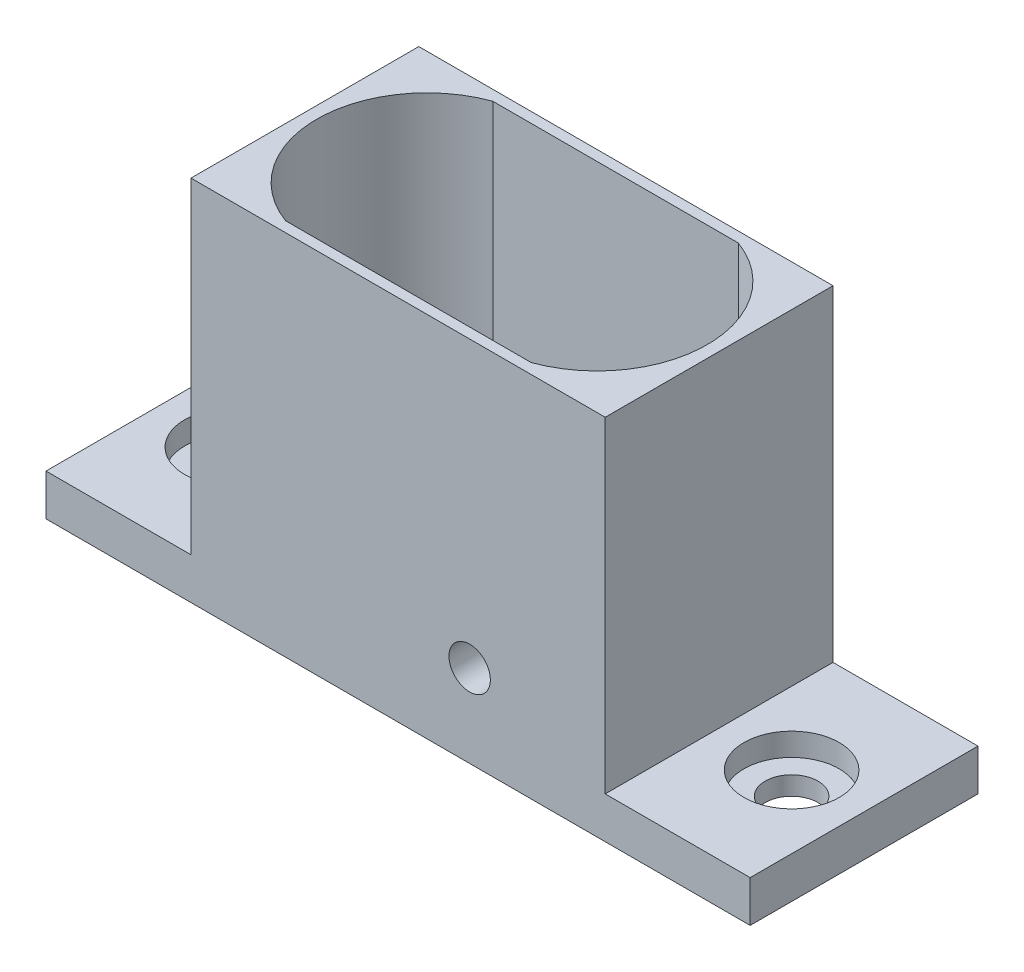
SolidWorks part; units mm, degrees
ref_plane "Front Plane" through (0, 0, 0) normal (0, 0, 1) x (1, 0, 0)
ref_plane "Top Plane" through (0, 0, 0) normal (0, 1, 0) x (1, 0, 0)
ref_plane "Right Plane" through (0, 0, 0) normal (1, 0, 0) x (0, 0, -1)
sketch "Sketch1" plane through (0, 0, 0) normal (0, 1, 0) x (1, 0, 0)
  line L0 (0, 19.2811) -> (0, -24.4507) construction
  line L1 (-34, -11) -> (34, -11)
  line L2 (-34, -11) -> (-34, 11)
  line L3 (-34, 11) -> (34, 11)
  line L4 (34, -11) -> (34, 11)
  line L5 (-34, -11) -> (34, 11) construction
  line L6 (-34, 11) -> (34, -11) construction
  line L7 (-20, 11) -> (-20, -11)
  line L8 (-11.8545, -10) -> (11.8545, -10)
  line L9 (-11.8545, 10) -> (11.8545, 10)
  line L10 (20, 11) -> (20, -11)
  line L12 (0.9292, -4.6) -> (12.9292, -4.6)
  line L13 (0.9292, -4.6) -> (0.9292, 4.6)
  line L14 (0.9292, 4.6) -> (12.9292, 4.6)
  line L15 (12.9292, -4.6) -> (12.9292, 4.6)
  line L16 (0.9292, -4.6) -> (12.9292, 4.6) construction
  line L17 (0.9292, 4.6) -> (12.9292, -4.6) construction
  circle A0 centre (-27, 0) radius 2.55
  circle A1 centre (-27, 0) radius 4.6
  arc A2 (-11.8545, 10) -> (-11.8545, -10) centre (-8.22, 0) ccw
  arc A3 (11.8545, 10) -> (11.8545, -10) centre (8.22, 0) cw
  circle A4 centre (27, 0) radius 2.55
  circle A5 centre (27, 0) radius 4.6
  point P0 (0, 0)
  point P16 (0, 10)
  point P24 (0, -10)
  point P26 (6.9292, 0)
  dimension "D4" = 5.1
  dimension "D5" = 9.2
  dimension "D7" = 21.28
  dimension "D8" = 1.14
  dimension "D1" = 68
  dimension "D2" = 22
  dimension "D3" = 7
  dimension "D6" = 14
  dimension "D9" = 1
  dimension "D10" = 1
  dimension "D11" = 6.4
  dimension "D12" = 7.0708
  dimension "D13" = 12
extrude "Boss-Extrude1" add sketch "Sketch1" along normal mid plane 35.5 contours L7 L3 L2 L1 A1 | A1 A0 | L10 L3 L7 L1 L9 A3 L8 A2 | A3 L9 A2 L8 L15 L12 L13 L14 | L12 L15 L14 L13 | L3 L10 L1 L4 A5 | A5 A4 region at (-33.7392, 0, 0) region at (-19.5435, 0, 0) region at (20.2608, 0, 0) region at (-1.3472, 0, 0) region at (6.9292, 0, 0) region at (-31.4699, 0, 0) region at (22.5301, 0, 0)
extrude "Cut-Extrude1" cut sketch "Sketch1<5>" against normal blind 31.5 from surface contours L7 L3 L2 L1 A1 | L3 L10 L1 L4 A5 | A1 A0 | A5 A4 region at (-33.7392, 0, 0) region at (20.2608, 0, 0) region at (-31.4699, 0, 0) region at (22.5301, 0, 0) starting at face at (0, 17.75, 0)
sketch "Sketch1<5>" plane through (0, 0, 0) normal (0, 1, 0) x (1, 0, 0) same geometry as "Sketch1"
extrude "Cut-Extrude2" cut sketch "Sketch1<6>" against normal blind 2.2 from surface contours A1 A0 | A5 A4 region at (-31.4699, 0, 0) region at (22.5301, 0, 0) starting at face at (-27, -13.75, 2.55)
sketch "Sketch1<6>" plane through (0, 0, 0) normal (0, 1, 0) x (1, 0, 0) same geometry as "Sketch1"
extrude "Cut-Extrude3" cut sketch "Sketch1<7>" against normal blind 23 from surface contours A3 L9 A2 L8 L15 L12 L13 L14 | L12 L15 L14 L13 region at (-1.3472, 0, 0) region at (6.9292, 0, 0) starting at face at (0, 17.75, 0)
sketch "Sketch1<7>" plane through (0, 0, 0) normal (0, 1, 0) x (1, 0, 0) same geometry as "Sketch1"
extrude "Cut-Extrude4" cut sketch "Sketch1<8>" against normal blind 9 from surface contours L12 L15 L14 L13 starting at face at (0, -5.25, 0)
sketch "Sketch1<8>" plane through (0, 0, 0) normal (0, 1, 0) x (1, 0, 0) same geometry as "Sketch1"
sketch "Sketch2" plane through (0, 0, -11) normal (0, 0, -1) x (-1, 0, 0)
  line L0 (-20, -13.75) -> (-20, 17.75) construction
  line L1 (34, -17.75) -> (-34, -17.75) construction
  circle A0 centre (-6.91, -9.77) radius 2
  circle A1 centre (-6.91, -9.77) radius 4.125
  dimension "D1" = 4
  dimension "D2" = 8.25
  dimension "D3" = 13.09
  dimension "D4" = 7.98
extrude "Cut-Extrude5" cut sketch "Sketch2" against normal up to surface (22 mm away) contours A0 region at (6.91, -9.77, -11) up to face at (0, -6.875, 11)
extrude "Cut-Extrude6" cut sketch "Sketch2<3>" against normal blind 2.5 contours A1
sketch "Sketch2<3>" plane through (0, 0, -11) normal (0, 0, -1) x (-1, 0, 0) same geometry as "Sketch2"
ref_plane "Plane2" through (6.9292, 0, 0) normal (1, 0, 0) x (0, 0, -1)
